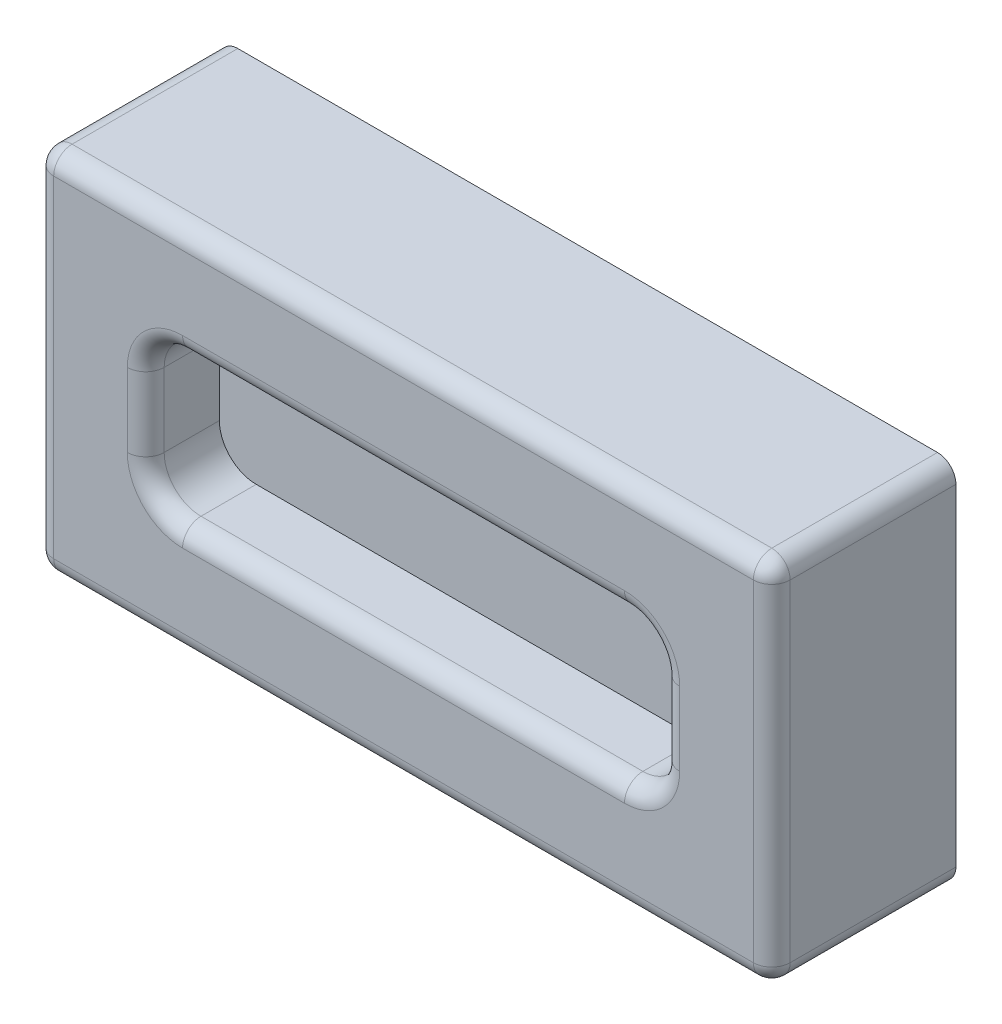
SolidWorks part; units mm, degrees
material "PVC hart"
ref_plane "Ebene vorne" through (0, 0, 0) normal (0, 0, 1) x (1, 0, 0)
ref_plane "Ebene oben" through (0, 0, 0) normal (0, 1, 0) x (1, 0, 0)
ref_plane "Ebene rechts" through (0, 0, 0) normal (1, 0, 0) x (0, 0, -1)
sketch "Skizze1" plane through (0, 0, 0) normal (0, 0, 1) x (1, 0, 0)
  line L1 (0, 0) -> (20, 0)
  line L2 (0, 0) -> (0, 10)
  line L3 (0, 10) -> (20, 10)
  line L4 (20, 0) -> (20, 10)
  dimension "D1" = 20
  dimension "D2" = 10
extrude "Aufsatz-Linear austragen1" add sketch "Skizze1" along normal blind 5
sketch "Skizze3" plane through (0, 0, 5) normal (0, 0, 1) x (1, 0, 0)
  line L0 (0, 10) -> (0, 0) construction
  line L1 (4, 7) -> (16, 7)
  line L2 (3, 6) -> (3, 4)
  line L3 (4, 3) -> (16, 3)
  line L4 (17, 6) -> (17, 4)
  line L5 (20, 10) -> (0, 10) construction
  arc A0 (3, 4) -> (4, 3) centre (4, 4) ccw
  arc A1 (16, 3) -> (17, 4) centre (16, 4) ccw
  arc A2 (16, 7) -> (17, 6) centre (16, 6) cw
  arc A3 (4, 7) -> (3, 6) centre (4, 6) ccw
  point P10 (3, 3)
  point P15 (17, 7)
  point P18 (3, 7)
  dimension "D5" = 1
  dimension "D1" = 14
  dimension "D2" = 3
  dimension "D3" = 4
  dimension "D4" = 3
extrude "Schnitt-Linear austragen2" cut sketch "Skizze3" against normal blind 2
fillet "Verrundung2" radius 0.5 8 edges at (16.7071, 6.7071, 5) (17, 5, 5) (16.7071, 3.2929, 5) (10, 3, 5) (3.2929, 3.2929, 5) (3, 5, 5) (3.2929, 6.7071, 5) (10, 7, 5)
fillet "Verrundung3" radius 0.5 4 edges at (10, 0, 5) (20, 5, 5) (10, 10, 5) (0, 5, 5)
fillet "Verrundung4" radius 0.5 2 edges at (19.8536, 9.8536, 4.8536) (20, 10, 2.25)
fillet "Verrundung5" radius 0.5 2 edges at (0.1464, 9.8536, 4.8536) (0, 10, 2.25)
fillet "Verrundung6" radius 0.5 2 edges at (0.1464, 0.1464, 4.8536) (0, 0, 2.25)
fillet "Verrundung7" radius 0.5 2 edges at (19.8536, 0.1464, 4.8536) (20, 0, 2.25)
